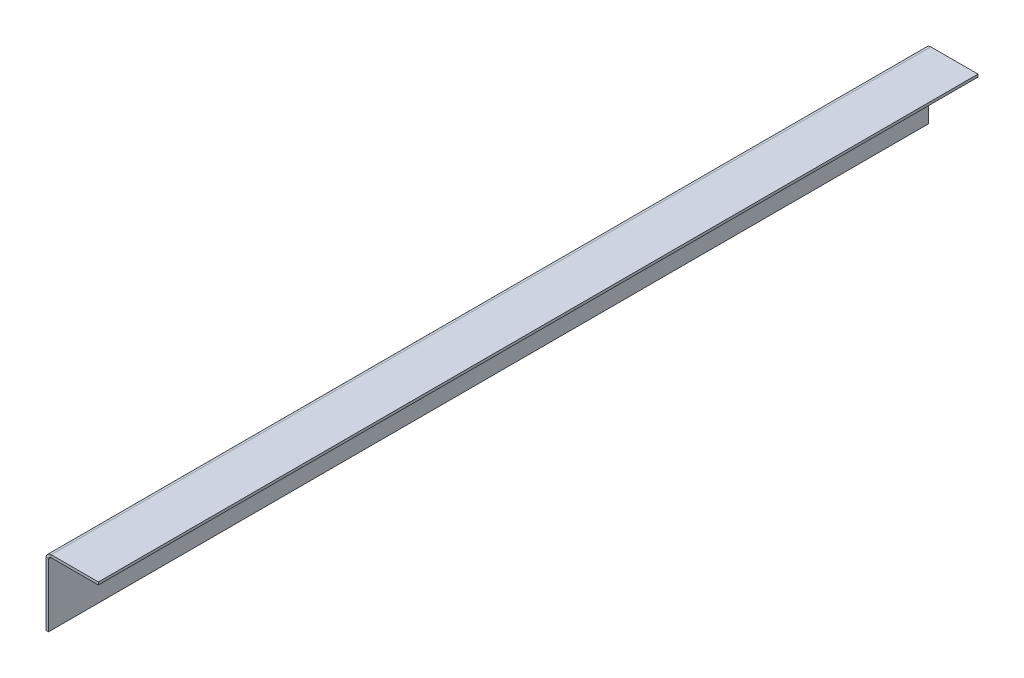
SolidWorks part; units mm, degrees
note: The reader was unsure of these and kept them because the rebuilt part matched: flange length of "Edge-Flange1".
material "5052-H32"
ref_plane "Front Plane" through (0, 0, 0) normal (0, 0, 1) x (1, 0, 0)
ref_plane "Top Plane" through (0, 0, 0) normal (0, 1, 0) x (1, 0, 0)
ref_plane "Right Plane" through (0, 0, 0) normal (1, 0, 0) x (0, 0, -1)
sketch "Sketch1" plane through (0, 0, 0) normal (1, 0, 0) x (0, 0, -1)
  line L0 (0, 0) -> (0, 82.55)
  line L3 (1066.8, 0) -> (1066.8, 82.55)
  line L20 (1066.8, 82.55) -> (0, 82.55)
  line L21 (1066.8, 0) -> (0, 0)
  dimension "D1" = 1066.8
  dimension "D2" = 82.55
  dimension "D9" = 82.55
base flange "Base-Flange1" sketch "Sketch1" thickness 3.175 reverse thickness direction no parameters "D1"=3.175
edge flange "Edge-Flange1" sketch "Sketch4" flange angle 90 flange length 63.5 flange position material inside bend radius 3.175 thickness 3.175 relief rectangular parameters "D6"=10
sketch "Sketch4" plane through (0, 82.55, 0) normal (0, 1, 0) x (0, 0, 1)
  line L0 (-1066.8, 0) -> (0, 0) construction
  line L1 (-1066.8, 0) -> (0, 0)
  line L2 (-1066.8, 0) -> (-1066.8, 60.325)
  line L3 (-1066.8, 60.325) -> (0, 60.325)
  line L4 (0, 60.325) -> (0, 0)
bend "EdgeBend1" bend radius 3.175 bend angle 90 parameters "D5"=1
sketch "Sketch9" plane through (0, 0, 0) normal (1, 0, 0) x (0, 0, -1)
  line L0 (0, 76.2) -> (1066.8, 76.2) construction
  line L1 (0, 76.2) -> (0, 0) construction
  line L2 (0, 0) -> (1066.8, 0) construction
  line L4 (1066.8, 0) -> (1066.8, 76.2) construction
  circle A0 centre (28.575, 63.5) radius 2.4574
  circle A1 centre (200.025, 63.5) radius 2.4575
  circle A2 centre (28.575, 15.875) radius 2.4574
  circle A3 centre (200.025, 15.875) radius 2.4574
  circle A4 centre (866.775, 63.5) radius 2.4575
  circle A5 centre (866.775, 15.875) radius 2.4575
  circle A6 centre (1038.225, 15.875) radius 2.4575
  circle A7 centre (1038.225, 63.5) radius 2.4575
  dimension "D5" = 4.9149
  dimension "D10" = 28.575
  dimension "D11" = 200.025
  dimension "D7" = 15.875
  dimension "D9" = 63.5
  dimension "D12" = 4.9149
  dimension "D1" = 12.7
  dimension "D2" = 28.575
  dimension "D3" = 47.625
  dimension "D4" = 171.45
  dimension "D6" = 63.5
  dimension "D8" = 15.875
extrude "Cut-Extrude1" [suppressed] cut sketch "Sketch9" against normal through all
sketch "Sketch10" plane through (0, 82.55, 0) normal (0, 1, 0) x (1, 0, 0)
  line L0 (15.875, 1066.8) -> (79.375, 1066.8)
  line L1 (60.325, 1066.8) -> (3.175, 1066.8) construction
  line L2 (15.875, 1066.8) -> (15.875, 666.75)
  line L3 (15.875, 666.75) -> (60.325, 666.75)
  line L4 (60.325, 0) -> (60.325, 1066.8) construction
  line L5 (60.325, 666.75) -> (60.325, 400.05)
  line L6 (60.325, 400.05) -> (15.875, 400.05)
  line L7 (15.875, 400.05) -> (15.875, 0)
  line L8 (3.175, 0) -> (60.325, 0) construction
  line L9 (15.875, 0) -> (79.375, 0)
  line L10 (79.375, 0) -> (79.375, 1066.8)
  line L11 (-3.175, 0) -> (-3.175, 1066.8) construction
  circle A0 centre (41.275, 650.875) radius 4.3688
  circle A1 centre (41.275, 415.925) radius 4.3688
  dimension "D8" = 8.7376
  dimension "D1" = 19.05
  dimension "D2" = 266.7
  dimension "D3" = 400.05
  dimension "D4" = 19.05
  dimension "D5" = 63.5
  dimension "D6" = 234.95
  dimension "D7" = 15.875
  dimension "D9" = 19.05
extrude "Cut-Extrude2" [suppressed] cut sketch "Sketch10" against normal blind 3.175
fillet "Fillet1" [suppressed] radius 6.35
sketch "Bend-Lines1" [suppressed] plane through (0, 0, 0) normal (0, 1, 0) x (1, 0, 0)
sketch "Bounding-Box1" [suppressed] plane through (0, 0, 0) normal (0, 1, 0) x (1, 0, 0)
sheet metal parameters "Sheet-Metal1" thickness 3.175 parameters "D1"=3.175
flat pattern "Flat-Pattern1" [suppressed]
sketch "Bend-Lines2" plane through (0, 0, 0) normal (0, 1, 0) x (1, 0, 0)
sketch3d "Bounding-Box2" [suppressed]
  line L0 (1066.8, 0, 0) -> (0, 0, 0) construction
  line L1 (1066.8, 73.025, 0) -> (0, 73.025, 0) construction
  line L2 (1066.8, 0, 0) -> (1066.8, 73.025, 0) construction
  line L3 (0, 0, 0) -> (0, 73.025, 0) construction
sheet metal parameters "Sheet-Metal9" thickness 3.175 parameters "D1"=3.175
flat pattern "Flat-Pattern1"
sketch "Bend-Lines2" plane through (0, 0, 0) normal (1, 0, 0) x (0, 0, -1)
  line L0 (1066.8, 79.9405) -> (0, 79.9405) construction
  line L1 (1066.8, 79.9405) -> (0, 79.9405) construction
sketch3d "Bounding-Box2" [suppressed]
  line L0 (1066.8, 0, 0) -> (0, 0, 0) construction
  line L1 (1066.8, 140.8309, 0) -> (0, 140.8309, 0) construction
  line L2 (1066.8, 0, 0) -> (1066.8, 140.8309, 0) construction
  line L3 (0, 0, 0) -> (0, 140.8309, 0) construction
bend of the flat pattern "Flatten-<EdgeBend1>1"
sheet metal parameters "Sheet-Metal10" thickness 3.175 parameters "D1"=3.175
flat pattern "Flat-Pattern1"
sketch "Bend-Lines2" plane through (0, 0, 0) normal (1, 0, 0) x (0, 0, -1)
  line L0 (1066.8, 79.9405) -> (0, 79.9405) construction
  line L1 (1066.8, 79.9405) -> (0, 79.9405) construction
  point P2 (0, -0.1873)
  point P3 (1066.7953, -0.1873)
sketch3d "Bounding-Box2" [suppressed]
  line L0 (1066.8, 0, 0) -> (0, 0, 0) construction
  line L1 (1066.8, 140.8309, 0) -> (0, 140.8309, 0) construction
  line L2 (1066.8, 0, 0) -> (1066.8, 140.8309, 0) construction
  line L3 (0, 0, 0) -> (0, 140.8309, 0) construction
bend of the flat pattern "Flatten-<EdgeBend1>1"
sheet metal parameters "Sheet-Metal11" thickness 3.175 parameters "D1"=3.175
flat pattern "Flat-Pattern1"
sketch "Bend-Lines2" plane through (0, 0, 0) normal (1, 0, 0) x (0, 0, -1)
  line L0 (1066.8, 79.9405) -> (0, 79.9405) construction
  line L1 (1066.8, 79.9405) -> (0, 79.9405) construction
sketch3d "Bounding-Box2" [suppressed]
  line L0 (1066.8, 140.8311, 0) -> (0, 140.8308, 0) construction
  line L1 (1066.8, 0.0003, 0) -> (0, 0, 0) construction
  line L2 (1066.8, 140.8311, 0) -> (1066.8, 0.0003, 0) construction
  line L3 (0, 140.8308, 0) -> (0, 0, 0) construction
bend of the flat pattern "Flatten-<EdgeBend1>1"
